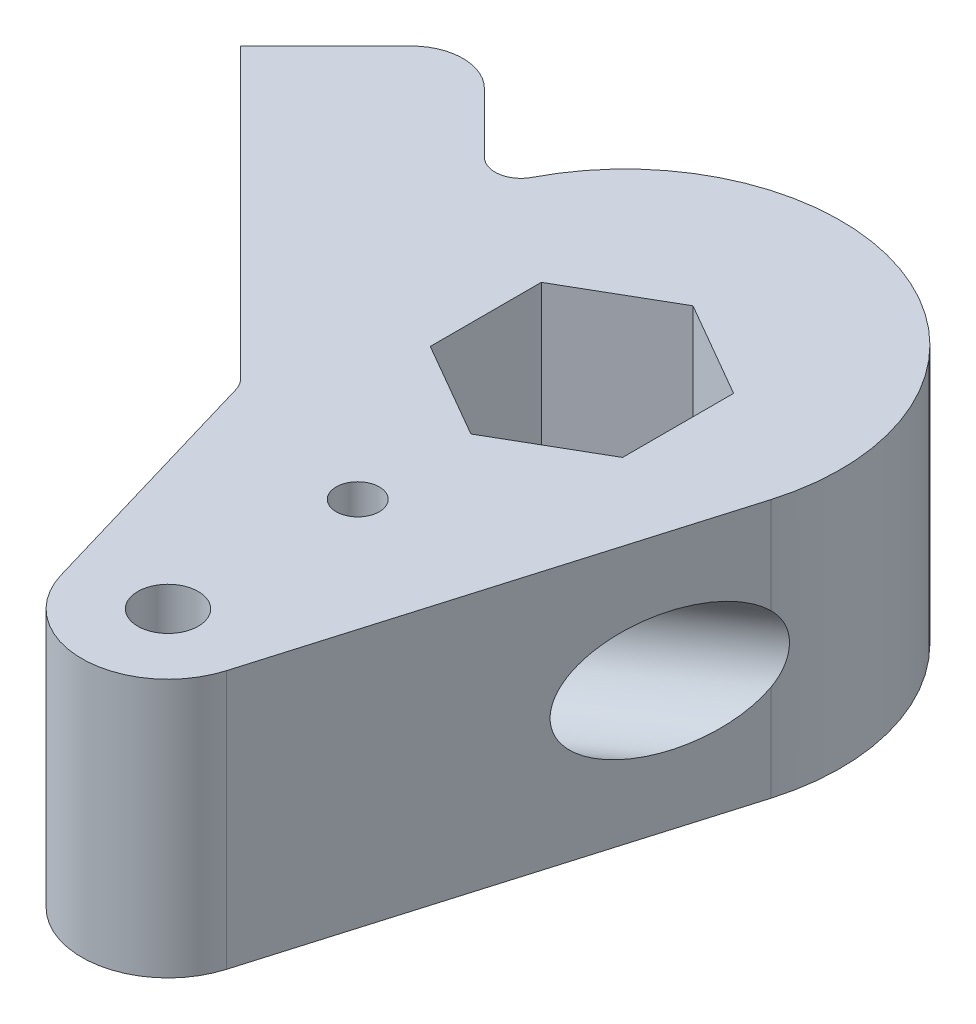
SolidWorks part; units mm, degrees
ref_plane "Front Plane" through (0, 0, 0) normal (0, 0, 1) x (1, 0, 0)
ref_plane "Top Plane" through (0, 0, 0) normal (0, 1, 0) x (1, 0, 0)
ref_plane "Right Plane" through (0, 0, 0) normal (1, 0, 0) x (0, 0, -1)
ref_axis "Axis1" through (0, 14.8656, 0) along (0, -1, 0)
sketch "Sketch1" plane through (0, 0, 0) normal (0, 1, 0) x (1, 0, 0)
  line L0 (0, 15) -> (0, -15) construction
  line L5 (-12.5, 15) -> (12.5, 15) construction
  line L7 (-12.5, 15) -> (-12.5, -15) construction
  line L10 (-12.5, -15) -> (12.5, -15) construction
  line L11 (12.5, 15) -> (12.5, -15) construction
  line L12 (-4.7956, -25.4151) -> (-11.9889, -1.0377)
  line L13 (0, -6.4375) -> (5.575, -3.2187)
  line L14 (5.575, -3.2187) -> (5.575, 3.2187)
  line L15 (5.575, 3.2187) -> (0, 6.4375)
  line L16 (0, 6.4375) -> (-5.575, 3.2187)
  line L17 (-5.575, 3.2187) -> (-5.575, -3.2187)
  line L18 (-5.575, -3.2187) -> (0, -6.4375)
  line L21 (11.9889, -1.0377) -> (4.7956, -25.4151)
  circle A0 centre (0, 0) radius 5.575 construction
  circle A1 centre (0, -24) radius 1.75
  arc A2 (-4.7956, -25.4151) -> (4.7956, -25.4151) centre (0, -24) ccw
  arc A4 (-11.9889, -1.0377) -> (11.9889, -1.0377) centre (0, 2.5) cw
  dimension "D3" = 15
  dimension "D4" = 11.15
  dimension "D5" = 24
  dimension "D1" = 25
  dimension "D6" = 3.5
  dimension "D7" = 5
  dimension "D2" = 30
extrude "Boss-Extrude1" add sketch "Sketch1" along normal blind 15
sketch "Sketch10" plane through (0, 0, 0) normal (0, 1, 0) x (1, 0, 0)
  circle A0 centre (0, -13) radius 1.25
  dimension "D2" = 2.5
  dimension "D1" = 13
extrude "Cut-Extrude3" cut sketch "Sketch10" along normal through all
ref_axis "Axis2" through (0, 15, 13) along (0, -1, 0)
ref_plane "Plane1" through (-6.108, 0, 4.2769) normal (0.8192, 0, -0.5736) x (0, -1, 0)
sketch "Sketch11" plane through (7.806, 0, 24.1481) normal (-0.8192, 0, 0.5736) x (0.5736, 0, 0.8192)
  line L1 (-12.3594, 15) -> (-14.8594, 15) construction
  line L3 (-12.3594, 15) -> (-14.8594, 15) construction
  line L4 (-13.6094, 15) -> (-13.6094, 0) construction
  line L5 (-14.8594, 0) -> (-12.3594, 0) construction
  line L6 (-14.8594, 0) -> (-12.3594, 0) construction
  circle A0 centre (-13.6094, 7.5) radius 2
  dimension "D1" = 4
extrude "Cut-Extrude4" cut sketch "Sketch11" against normal through all
sketch "Sketch12" plane through (0, 0, 0) normal (0, 1, 0) x (1, 0, 0)
  line L12 (5.575, -3.2187) -> (5.575, 3.2187) construction
  line L13 (0, -6.4375) -> (5.575, -3.2187) construction
  line L14 (-5.575, -3.2187) -> (0, -6.4375) construction
  line L15 (-5.575, 3.2187) -> (-5.575, -3.2187) construction
  line L16 (0, 6.4375) -> (-5.575, 3.2187) construction
  line L17 (5.575, 3.2187) -> (0, 6.4375) construction
  line L18 (5.575, -3.2187) -> (5.575, 3.2187)
  line L19 (0, -6.4375) -> (5.575, -3.2187)
  line L20 (-5.575, -3.2187) -> (0, -6.4375)
  line L21 (-5.575, 3.2187) -> (-5.575, -3.2187)
  line L22 (0, 6.4375) -> (-5.575, 3.2187)
  line L23 (5.575, 3.2187) -> (0, 6.4375)
  circle A0 centre (0, 0) radius 3.5
  dimension "D1" = 7
extrude "Boss-Extrude8" add sketch "Sketch12" along normal blind 5
sketch "Sketch13" plane through (0, 0, 0) normal (0, 1, 0) x (1, 0, 0)
  line L0 (0, 0) -> (0, -24) construction
  line L1 (-19.0919, 13.435) -> (-26.163, 6.364)
  line L2 (-19.0919, 13.435) -> (-0.9289, -4.7279) construction
  line L3 (-26.163, 6.364) -> (-8, -11.799)
  line L4 (-0.9289, -4.7279) -> (-8, -11.799) construction
  line L5 (-19.0919, 13.435) -> (-8, -11.799) construction
  line L6 (-26.163, 6.364) -> (-0.9289, -4.7279) construction
  line L7 (-19.0919, 13.435) -> (-8, 2.3431)
  line L8 (-8, 2.3431) -> (-8, -11.799)
  point P5 (-13.5459, 0.818)
  dimension "D1" = 10
  dimension "D2" = 23
  dimension "D3" = 45
  dimension "D4" = 14
  dimension "D5" = 8
extrude "Boss-Extrude9" add sketch "Sketch13" along normal up to surface (15 mm away) up to face at (0, 15, 14.25)
sketch "Sketch14" plane through (-9.8995, 0, 9.8995) normal (-0.7071, 0, 0.7071) x (0.7071, 0, 0.7071)
  line L0 (-18, 15) -> (-18, 0) construction
  line L1 (-23, 15) -> (1.0543, 15) construction
  line L2 (-23, 0) -> (1.0543, 0) construction
  line L3 (-23, 15) -> (-23, 0) construction
  circle A0 centre (-18, 7.5) radius 2.8
  dimension "D1" = 5
  dimension "D2" = 5.6
extrude "Cut-Extrude5" cut sketch "Sketch14" against normal through all
fillet "Fillet1" radius 3 1 edges at (-19.0919, 7.5, -13.435)
fillet "Fillet2" radius 1.5 2 edges at (-9.154, 7.5, 10.645) (-11.9201, 7.5, -6.2632)
ref_plane "Plane2" through (10.275, 0, -7.1947) normal (0.8192, 0, -0.5736) x (0, -1, 0)
sketch "Sketch15" plane through (10.275, 0, -7.1947) normal (0.8192, 0, -0.5736) x (0, -1, 0)
  circle A0 centre (-7.5, -10.649) radius 2 construction
  circle A1 centre (-7.5, -10.649) radius 2 construction
  circle A2 centre (-7.5, -10.649) radius 3.5
  dimension "D1" = 7
extrude "Cut-Extrude6" cut sketch "Sketch15" against normal offset from surface (13 mm away) 7 up to plane "Plane1"
